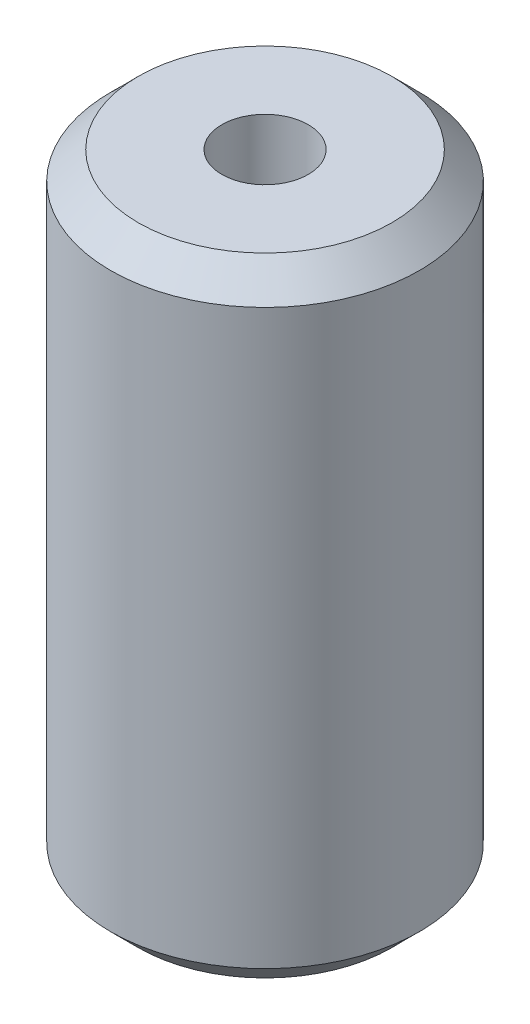
SolidWorks part; units mm, degrees
ref_plane "Front Plane" through (0, 0, 0) normal (0, 0, 1) x (1, 0, 0)
ref_plane "Top Plane" through (0, 0, 0) normal (0, 1, 0) x (1, 0, 0)
ref_plane "Right Plane" through (0, 0, 0) normal (1, 0, 0) x (0, 0, -1)
sketch "Sketch1" plane through (0, 0, 0) normal (0, 1, 0) x (1, 0, 0)
  circle A0 centre (0, 0) radius 20
  dimension "SHAFT_OD" = 40
extrude "Boss-Extrude1" add sketch "Sketch1" along normal blind 81.3196
sketch "Sketch2" plane through (0, 0, 0) normal (0, 1, 0) x (1, 0, 0)
  circle A0 centre (0, 0) radius 5.5935
  dimension "BORE_D" = 11.187
extrude "Cut-Extrude1" cut sketch "Sketch2" along normal through all
chamfer "Chamfer1" distance 3.5746 angle 45 2 edges at (0, 81.3196, 20) (0, 0, 20)
